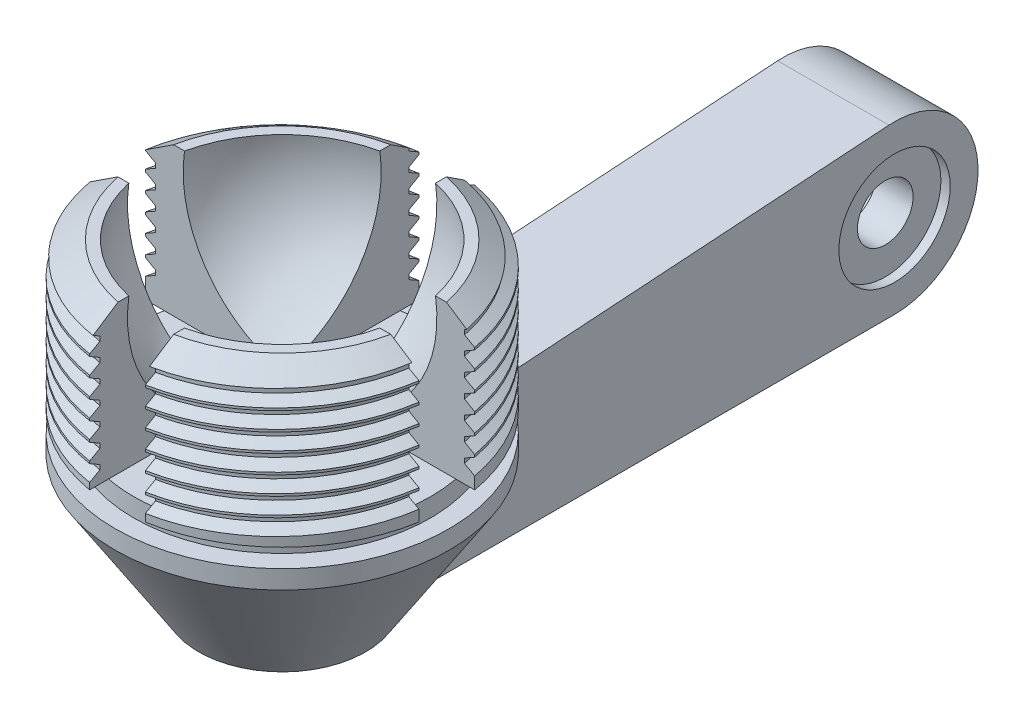
SolidWorks part; units mm, degrees
ref_plane "Front Plane" through (0, 0, 0) normal (0, 0, 1) x (1, 0, 0)
ref_plane "Top Plane" through (0, 0, 0) normal (0, 1, 0) x (1, 0, 0)
ref_plane "Right Plane" through (0, 0, 0) normal (1, 0, 0) x (0, 0, -1)
sketch "Sketch1" plane through (0, 0, 0) normal (0, 0, 1) x (1, 0, 0)
  line L0 (0, 9) -> (0, 7)
  line L1 (0, -16) -> (4.5, -16)
  line L3 (0, -7) -> (0, -16)
  line L4 (9, -9) -> (9, 9)
  line L5 (9, 9) -> (0, 9)
  line L7 (4.5, -16) -> (9, -9)
  arc A2 (0, -7) -> (0, 7) centre (0, 0) ccw
  point P5 (0, 8)
  dimension "D1" = 18
  dimension "D2" = 9
  dimension "D5" = 14
  dimension "D3" = 25
  dimension "D4" = 4.5
  dimension "D6" = 9
revolve "Revolve1" add sketch "Sketch1" angle 360 about L0
sketch "Sketch2" plane through (0, 0, 0) normal (0, 0, 1) x (1, 0, 0)
  line L0 (-9, 1) -> (9, 1)
  line L1 (-9, 9) -> (9, 9)
  line L2 (-9, 9) -> (-9, 1)
  line L4 (9, 9) -> (9, 1)
  point P4 (0, 9)
  point P7 (0, 1)
  dimension "D1" = 8
  dimension "D2" = 9
  dimension "D3" = 18
extrude "Cut-Extrude1" cut sketch "Sketch2" against normal through all both and the other way through all
sketch "Sketch18" plane through (0, 1, 0) normal (0, 1, 0) x (1, 0, 0)
  line L0 (1.5, 1.5) -> (9, 1.5)
  line L1 (-1.5, 9) -> (1.5, 9)
  line L2 (-1.5, 9) -> (-1.5, 1.5)
  line L3 (-1.5, -9) -> (1.5, -9)
  line L4 (1.5, 9) -> (1.5, 1.5)
  line L5 (-9, 1.5) -> (-1.5, 1.5)
  line L6 (-9, 1.5) -> (-9, -1.5)
  line L7 (-9, -1.5) -> (-1.5, -1.5)
  line L8 (9, 1.5) -> (9, -1.5)
  line L9 (-1.5, -1.5) -> (-1.5, -9)
  line L10 (1.5, -1.5) -> (1.5, -9)
  line L11 (1.5, -1.5) -> (9, -1.5)
  point P4 (0, 9)
  point P11 (-9, 0)
  dimension "D2" = 3
  dimension "D3" = 18
extrude "Cut-Extrude8" cut sketch "Sketch18" against normal blind 8
thread "Thread3" pitch 1 start angle 0, offset 0, length 0, pitch 1, diameter 18
ref_plane "Plane4" through (-9, 1, 0) normal (0, 0, 1) x (-1, 0, 0)
sketch "Thread Profile4" plane through (-9, 1, 0) normal (0, 0, 1) x (-1, 0, 0)
  line L0 (0, 0) -> (0, 1) construction
  line L11 (0, 0) -> (0, 0.875)
  line L12 (0, 0.875) -> (-0.5413, 0.5625)
  line L13 (-0.5413, 0.5625) -> (-0.5413, 0.3125)
  line L15 (-0.5413, 0.3125) -> (0, 0)
  line L17 (-0.5413, 0.4375) -> (0, 0.4375) construction
  point P2 (0, 0)
  dimension "Pitch" = 1
  dimension "Profile_Angle" = 60
  dimension "Profile_Land" = 0.25
  dimension "Profile_Height" = 0.5413
sketch "Sketch23" plane through (0, 0, 0) normal (1, 0, 0) x (0, 0, -1)
  line L0 (-9, -9) -> (9, -9) construction
  line L1 (29.7003, -7.01) -> (-0.2331, -9.0078)
  line L2 (30, -16) -> (0, -16)
  line L4 (-4.5, -16) -> (4.5, -16) construction
  arc A2 (-0.2331, -9.0078) -> (0, -16) centre (0, -12.5) ccw
  arc A3 (30, -16) -> (29.7003, -7.01) centre (30, -11.5) ccw
  dimension "D1" = 9
  dimension "D2" = 7
  dimension "D3" = 30
extrude "Boss-Extrude1" add sketch "Sketch23" along normal mid plane 6
sketch "Sketch24" plane through (-3, 0, 0) normal (-1, 0, 0) x (0, 0, 1)
  circle A0 centre (-30, -11.5) radius 3
  arc A2 (-29.7003, -7.01) -> (-30, -16) centre (-30, -11.5) ccw construction
  dimension "D1" = 6
extrude "Cut-Extrude9" cut sketch "Sketch24" against normal blind 3.5
sketch "Sketch25" plane through (3, 0, 0) normal (1, 0, 0) x (0, 0, -1)
  circle A0 centre (30, -11.5) radius 3
  arc A2 (30, -16) -> (29.7003, -7.01) centre (30, -11.5) ccw construction
  dimension "D1" = 6
extrude "Cut-Extrude10" cut sketch "Sketch25" against normal blind 0.5
sketch "Sketch26" plane through (2.5, 0, 0) normal (1, 0, 0) x (0, 0, -1)
  circle A0 centre (30, -11.5) radius 1.5
  dimension "D1" = 3
extrude "Cut-Extrude11" cut sketch "Sketch26" against normal through all
sketch "Sketch27" plane through (0, 0, 0) normal (1, 0, 0) x (0, 0, -1)
  line L0 (0, 0) -> (0, -4.1983) construction
  line L1 (7.5, 1) -> (9, 1)
  line L2 (8.8741, 1) -> (1.5, 1) construction
  line L3 (9, 1) -> (9, 0)
  line L4 (9, 0) -> (7.5, 1)
  line L5 (9, -8.3915) -> (9, -7) construction
  line L7 (9, -7) -> (8, -7)
  line L8 (9, -7) -> (9, -8)
  line L9 (9, -8) -> (8, -8)
  line L10 (8, -7) -> (8, -8)
  dimension "D1" = 1
  dimension "D2" = 1.5
  dimension "D3" = 1
  dimension "D4" = 1
revolve "Cut-Revolve1" cut sketch "Sketch27" angle 360 about L0
